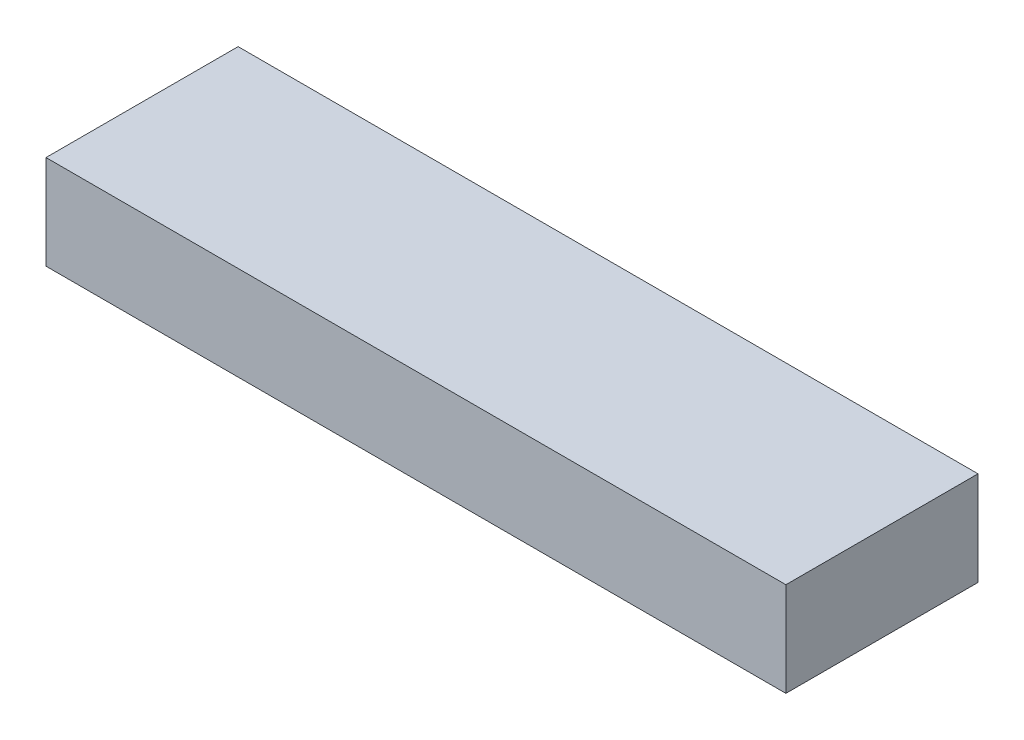
SolidWorks part; units mm, degrees
ref_plane "Front Plane" through (0, 0, 0) normal (0, 0, 1) x (1, 0, 0)
ref_plane "Top Plane" through (0, 0, 0) normal (0, 1, 0) x (1, 0, 0)
ref_plane "Right Plane" through (0, 0, 0) normal (1, 0, 0) x (0, 0, -1)
sketch "Sketch1" plane through (0, 0, 0) normal (0, 1, 0) x (1, 0, 0)
  line L1 (570, -148) -> (-570, -148)
  line L2 (570, -148) -> (570, 148)
  line L3 (570, 148) -> (-570, 148)
  line L4 (-570, -148) -> (-570, 148)
  line L5 (570, -148) -> (-570, 148) construction
  line L6 (570, 148) -> (-570, -148) construction
  point P0 (0, 0)
  dimension "D1" = 1140
  dimension "D2" = 296
extrude "Boss-Extrude1" add sketch "Sketch1" along normal blind 145
equation "\"thickness 1\" = 2"
equation "\"thickness 2\"= 3"
equation "\"connecting flange\"= 35"
equation "\"main length\"= 1200"
equation "\"main width\"= 1200"
equation "\"divider panel distance offset\"= 296"
equation "\"access hatch length\" = \"access hatch cutout length\" + \"access hatch offset\" * 2"
equation "\"access hatch width\" = \"access hatch cutout width\" + \"access hatch offset\" * 2"
equation "\"side panel length\"= 1200"
equation "\"side panel width\"= 950"
equation "\"drift eliminator size offset\"= 5"
equation "\"drift eliminator depth\" = \"divider panel distance offset\""
equation "\"D2@Sketch1\"=\"drift eliminator depth\""
equation "\"thickness radius 1\"= 3.7366"
equation "\"connecting flange holes\"= 8"
equation "\"connecting flange hole gap\"= 100"
equation "\"cut out flange\"= 15 "
equation "\"top panel slot length\"= 250"
equation "\"top panel slot width\"= 700"
equation "\"access hatch cutout length\"= 400"
equation "\"access hatch cutout width\"= 600"
equation "\"access hatch cutout offset X\"= 100"
equation "\"access hatch cutout offset Y\"= 100"
equation "\"slotted panel length\" = \"main length\" + 100"
equation "\"slotted panel width\" = \"main width\""
equation "\"slot count x\"= 3"
equation "\"slot count y\"= 11"
equation "\"slot offset\" = \"water tray depth\""
equation "\"slot length\"= 30"
equation "\"slot width\"= 200"
equation "\"slot offset x\" = \"slot length\" + \"slot offset\""
equation "\"slot offset y\" = \"slot width\" + \"slot offset\""
equation "\"guide rail flange\"= 40"
equation "\"guid rail flange mount side\"= 20"
equation "\"guid rail back length\" = \"main width\" - \"guide rail flange\" * 2"
equation "\"splash plate length\"= 400"
equation "\"splash plate width\" = \"main width\""
equation "\"splash plate air gap\"= 200"
equation "\"splash plate slot count\"= 11"
equation "\"splash plate slot length\"= 50"
equation "\"splash plate slot height\"= 50"
equation "\"splash plate slot offset\"= 65"
equation "\"water tray depth\"= 150"
equation "\"water tray width\"= 200"
equation "\"water tray panel length\"= 473"
equation "\"dimpled panel length\" = \"main length\" - 200 - \"water tray depth\"/2"
equation "\"dimpled panel top offset\" = \"water tray depth\"/2"
equation "\"dimpled panel width\" = \"main width\""
equation "\"dimple panel slot count\"= 119"
equation "\"dimple panel slot length\"= 10"
equation "\"dimple panel slot width\"= 5"
equation "\"dimple panel slot offset\"= 10"
equation "\"sump base flat section width\"= 300"
equation "\"sump upper depth\"= 300"
equation "\"sump depth\"= 550"
equation "\"leg length\" = \"sump depth\" + 150"
equation "\"leg width\"= 80"
equation "\"leg depth\"= 40"
equation "\"leg support plate size\" = \"leg width\" - \"thickness 2\" * 2"
equation "\"leg base plate thickness\"= 8"
